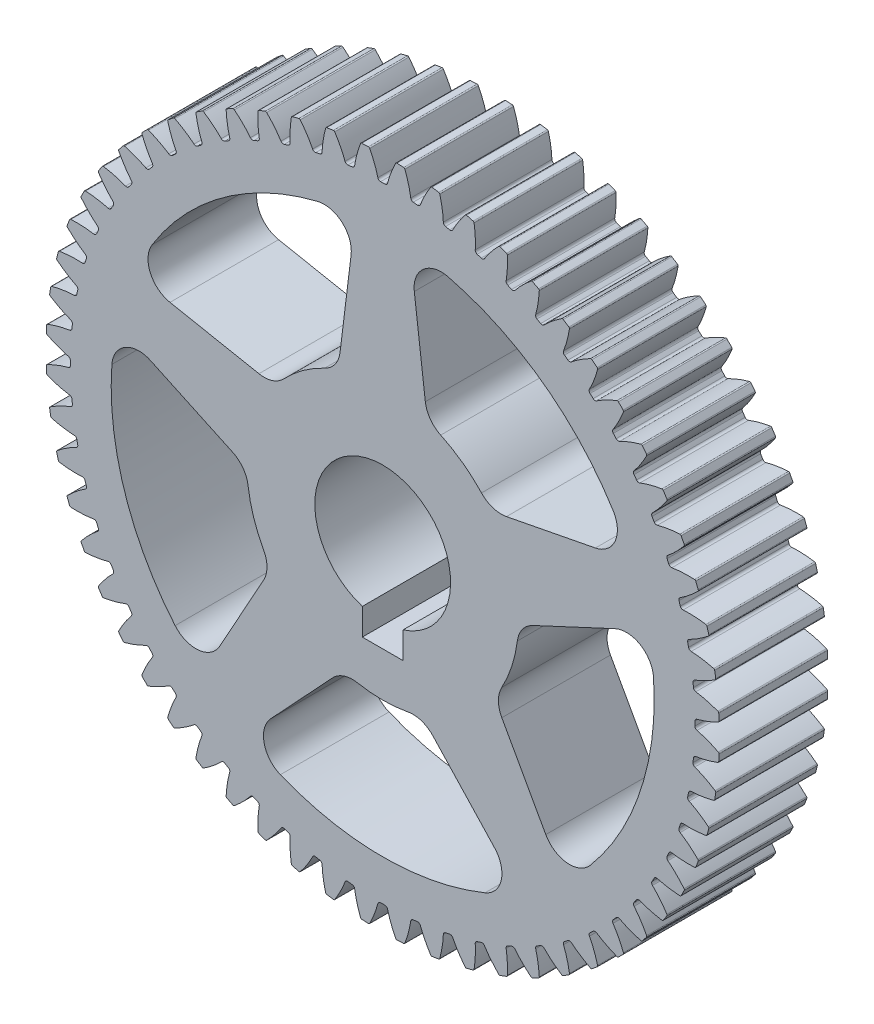
SolidWorks part; units mm, degrees
material "Alloy Steel"
ref_plane "Front" through (0, 0, 0) normal (0, 0, 1) x (1, 0, 0)
ref_plane "Top" through (0, 0, 0) normal (0, 1, 0) x (1, 0, 0)
ref_plane "Right" through (0, 0, 0) normal (1, 0, 0) x (0, 0, -1)
sketch "Sketch1" plane through (0, 0, 0) normal (0, 0, 1) x (1, 0, 0)
  circle A0 centre (0, 0) radius 39.37
  dimension "OutsideDiameter" = 78.74
extrude "Boss-Extrude1" add sketch "Sketch1" along normal blind 12.7
sketch "Sketch3" plane through (0, 0, 0) normal (0, 0, 1) x (1, 0, 0)
  line L0 (0, 0) -> (43.7181, 0) construction
  line L2 (0, 0) -> (-0.4117, 36.5102) construction
  line L3 (0, 0) -> (0.4117, 36.5102) construction
  line L4 (0.4117, 36.5102) -> (0.4037, 35.8) construction
  line L5 (0, 0) -> (0, 61.276) construction
  line L6 (-0.4117, 36.5102) -> (-0.4037, 35.8) construction
  circle A0 centre (0, 0) radius 39.37 construction
  circle A1 centre (0, 0) radius 38.1 construction
  circle A2 centre (0, 0) radius 35.8023 construction
  arc A3 (0.4117, 36.5102) -> (-0.4117, 36.5102) centre (0, 0) ccw construction
  arc A5 (1.5621, 39.339) -> (-1.5621, 39.339) centre (0, 0) ccw
  spline S0 degree 4 poles (-0.4037, 35.8) (-0.4038, 35.8056) (-0.4043, 35.8211) (-0.4059, 35.8504) (-0.4094, 35.8983) (-0.4152, 35.9593) (-0.4244, 36.0381) (-0.4372, 36.1309) (-0.4533, 36.2329) (-0.4732, 36.3438) (-0.4951, 36.4544) (-0.5188, 36.5646) (-0.5442, 36.6744) (-0.5769, 36.8074) (-0.6189, 36.9667) (-0.6721, 37.1529) (-0.7372, 37.3638) (-0.8088, 37.5787) (-0.8835, 37.7899) (-0.9639, 38.0031) (-1.0452, 38.2093) (-1.1346, 38.4233) (-1.2197, 38.6207) (-1.3206, 38.8416) (-1.4037, 39.0199) (-1.5193, 39.2547) (-1.5893, 39.3933) (-1.6733, 39.5555) (-1.7117, 39.6274) (-1.7353, 39.6717) knots 0 0 0 0 0 0.005377 0.015084 0.028532 0.04661 0.064855 0.092111 0.119476 0.146842 0.174209 0.201575 0.228941 0.256307 0.307035 0.361767 0.4165 0.471232 0.525964 0.580697 0.635429 0.690161 0.744894 0.799626 0.854358 0.909091 0.954545 1 1 1 1 1 construction
  spline S1 degree 4 poles (-0.4037, 35.8) (-0.4038, 35.8056) (-0.4043, 35.8211) (-0.4059, 35.8504) (-0.4094, 35.8983) (-0.4152, 35.9593) (-0.4244, 36.0381) (-0.4372, 36.1309) (-0.4533, 36.2329) (-0.4732, 36.3438) (-0.4951, 36.4544) (-0.5188, 36.5646) (-0.5442, 36.6744) (-0.5769, 36.8074) (-0.6189, 36.9667) (-0.6721, 37.1529) (-0.7372, 37.3638) (-0.8088, 37.5787) (-0.8835, 37.7899) (-0.9639, 38.0031) (-1.0452, 38.2093) (-1.1346, 38.4233) (-1.2197, 38.6207) (-1.3206, 38.8416) (-1.4037, 39.0199) (-1.4942, 39.2038) (-1.539, 39.2933) (-1.5621, 39.339) knots 0 0 0 0 0 0.005377 0.015084 0.028532 0.04661 0.064855 0.092111 0.119476 0.146842 0.174209 0.201575 0.228941 0.256307 0.307035 0.361767 0.4165 0.471232 0.525964 0.580697 0.635429 0.690161 0.744894 0.799626 0.854358 0.909091 0.909091 0.909091 0.909091 0.909091
  spline S2 degree 4 poles (0.4037, 35.8) (0.4038, 35.8056) (0.4043, 35.8211) (0.4059, 35.8504) (0.4094, 35.8983) (0.4152, 35.9593) (0.4244, 36.0381) (0.4372, 36.1309) (0.4533, 36.2329) (0.4732, 36.3438) (0.4951, 36.4544) (0.5188, 36.5646) (0.5442, 36.6744) (0.5769, 36.8074) (0.6189, 36.9667) (0.6721, 37.1529) (0.7372, 37.3638) (0.8088, 37.5787) (0.8835, 37.7899) (0.9639, 38.0031) (1.0452, 38.2093) (1.1346, 38.4233) (1.2197, 38.6207) (1.3206, 38.8416) (1.4037, 39.0199) (1.5193, 39.2547) (1.5893, 39.3933) (1.6733, 39.5555) (1.7117, 39.6274) (1.7353, 39.6717) knots 0 0 0 0 0 0.005377 0.015084 0.028532 0.04661 0.064855 0.092111 0.119476 0.146842 0.174209 0.201575 0.228941 0.256307 0.307035 0.361767 0.4165 0.471232 0.525964 0.580697 0.635429 0.690161 0.744894 0.799626 0.854358 0.909091 0.954545 1 1 1 1 1 construction
  spline S3 degree 4 poles (0.4037, 35.8) (0.4038, 35.8056) (0.4043, 35.8211) (0.4059, 35.8504) (0.4094, 35.8983) (0.4152, 35.9593) (0.4244, 36.0381) (0.4372, 36.1309) (0.4533, 36.2329) (0.4732, 36.3438) (0.4951, 36.4544) (0.5188, 36.5646) (0.5442, 36.6744) (0.5769, 36.8074) (0.6189, 36.9667) (0.6721, 37.1529) (0.7372, 37.3638) (0.8088, 37.5787) (0.8835, 37.7899) (0.9639, 38.0031) (1.0452, 38.2093) (1.1346, 38.4233) (1.2197, 38.6207) (1.3206, 38.8416) (1.4037, 39.0199) (1.4942, 39.2038) (1.539, 39.2933) (1.5621, 39.339) knots 0 0 0 0 0 0.005377 0.015084 0.028532 0.04661 0.064855 0.092111 0.119476 0.146842 0.174209 0.201575 0.228941 0.256307 0.307035 0.361767 0.4165 0.471232 0.525964 0.580697 0.635429 0.690161 0.744894 0.799626 0.854358 0.909091 0.909091 0.909091 0.909091 0.909091
  dimension "OutsideDiameter" = 78.74
  dimension "PitchCircle" = 76.2
  dimension "BaseCircle" = 71.6046
  dimension "DedendumCircle" = 73.025
sketch "DCLTBC" [suppressed] plane through (0, 0, 0) normal (0, 0, 1) x (1, 0, 0)
  line L0 (0, 0) -> (41.04, 0) construction
  line L1 (-0.5882, 26.2434) -> (-0.5952, 26.5563) construction
  line L2 (0.5882, 26.2434) -> (0.5952, 26.5563) construction
  line L3 (-0.5936, 26.4814) -> (-0.5952, 26.5563)
  line L4 (0.5936, 26.4814) -> (0.5952, 26.5563)
  line L5 (0, 0) -> (0, 104.9356) construction
  circle A0 centre (0, 0) radius 28.5
  circle A1 centre (0, 0) radius 27.5 construction
  circle A2 centre (0, 0) radius 26.563 construction
  arc A3 (0.5882, 26.2434) -> (-0.5882, 26.2434) centre (0, 0) ccw construction
  arc A4 (0.3512, 26.2477) -> (-0.3512, 26.2477) centre (0, 0) ccw
  arc A5 (-0.5936, 26.4814) -> (-0.3512, 26.2477) centre (-0.3544, 26.4868) ccw
  arc A7 (0.5936, 26.4814) -> (0.3512, 26.2477) centre (0.3544, 26.4868) cw
  spline S0 degree 4 poles (-999.0854, -27.9057) (-10.5882, 25.1883) (-0.7108, 25.7707) (-0.5671, 26.1913) (-0.5985, 26.609) (-0.6016, 26.6417) (-0.6063, 26.6839) (-0.6128, 26.7337) (-0.6209, 26.7885) (-0.6307, 26.8481) (-0.6414, 26.9075) (-0.653, 26.9669) (-0.6654, 27.026) (-0.6812, 27.0976) (-0.7015, 27.1836) (-0.7271, 27.2842) (-0.7584, 27.3983) (-0.7927, 27.5147) (-0.8284, 27.6294) (-0.8667, 27.7454) (-0.9054, 27.8577) (-0.948, 27.9745) (-0.9884, 28.0824) (-1.0364, 28.2034) (-1.2469, 28.7251) (-2.0615, 30.5023) (8.679, 5.7048) (-401.0337, 945.0216) knots -0.712101 -0.712101 -0.712101 -0.712101 -0.712101 0.005377 0.015084 0.028532 0.04661 0.064855 0.092111 0.119476 0.146842 0.174209 0.201575 0.228941 0.256307 0.307035 0.361767 0.4165 0.471232 0.525964 0.580697 0.635429 0.690161 0.744894 0.799626 0.854358 1.858481 1.858481 1.858481 1.858481 1.858481 only from (-0.5952, 26.5563) to (-1.151, 28.4767) construction
  spline S1 degree 4 poles (999.0854, -27.9056) (10.5882, 25.1883) (0.7108, 25.7707) (0.5671, 26.1913) (0.5985, 26.609) (0.6016, 26.6417) (0.6063, 26.6839) (0.6128, 26.7337) (0.6209, 26.7885) (0.6307, 26.8481) (0.6414, 26.9075) (0.653, 26.9669) (0.6654, 27.026) (0.6812, 27.0976) (0.7015, 27.1836) (0.7271, 27.2842) (0.7584, 27.3983) (0.7927, 27.5147) (0.8284, 27.6294) (0.8667, 27.7454) (0.9054, 27.8577) (0.948, 27.9745) (0.9884, 28.0824) (1.0364, 28.2034) (1.2469, 28.7251) (2.0615, 30.5023) (-8.679, 5.7048) (401.0337, 945.0216) knots -0.712101 -0.712101 -0.712101 -0.712101 -0.712101 0.005377 0.015084 0.028532 0.04661 0.064855 0.092111 0.119476 0.146842 0.174209 0.201575 0.228941 0.256307 0.307035 0.361767 0.4165 0.471232 0.525964 0.580697 0.635429 0.690161 0.744894 0.799626 0.854358 1.858481 1.858481 1.858481 1.858481 1.858481 only from (0.5952, 26.5563) to (1.151, 28.4767) construction
  spline S2 degree 4 poles (-0.5952, 26.5563) (-0.5953, 26.5593) (-0.5957, 26.5676) (-0.5966, 26.5833) (-0.5985, 26.609) (-0.6016, 26.6417) (-0.6063, 26.6839) (-0.6128, 26.7337) (-0.6209, 26.7885) (-0.6307, 26.8481) (-0.6414, 26.9075) (-0.653, 26.9669) (-0.6654, 27.026) (-0.6812, 27.0976) (-0.7015, 27.1836) (-0.7271, 27.2842) (-0.7584, 27.3983) (-0.7927, 27.5147) (-0.8284, 27.6294) (-0.8667, 27.7454) (-0.9054, 27.8577) (-0.948, 27.9745) (-0.9884, 28.0824) (-1.0364, 28.2034) (-1.0758, 28.3012) (-1.1188, 28.4023) (-1.14, 28.4516) (-1.151, 28.4767) knots 0 0 0 0 0 0.005377 0.015084 0.028532 0.04661 0.064855 0.092111 0.119476 0.146842 0.174209 0.201575 0.228941 0.256307 0.307035 0.361767 0.4165 0.471232 0.525964 0.580697 0.635429 0.690161 0.744894 0.799626 0.854358 0.909091 0.909091 0.909091 0.909091 0.909091
  spline S3 degree 4 poles (0.5952, 26.5563) (0.5953, 26.5593) (0.5957, 26.5676) (0.5966, 26.5833) (0.5985, 26.609) (0.6016, 26.6417) (0.6063, 26.6839) (0.6128, 26.7337) (0.6209, 26.7885) (0.6307, 26.8481) (0.6414, 26.9075) (0.653, 26.9669) (0.6654, 27.026) (0.6812, 27.0976) (0.7015, 27.1836) (0.7271, 27.2842) (0.7584, 27.3983) (0.7927, 27.5147) (0.8284, 27.6294) (0.8667, 27.7454) (0.9054, 27.8577) (0.948, 27.9745) (0.9884, 28.0824) (1.0364, 28.2034) (1.0758, 28.3012) (1.1188, 28.4023) (1.14, 28.4516) (1.151, 28.4767) knots 0 0 0 0 0 0.005377 0.015084 0.028532 0.04661 0.064855 0.092111 0.119476 0.146842 0.174209 0.201575 0.228941 0.256307 0.307035 0.361767 0.4165 0.471232 0.525964 0.580697 0.635429 0.690161 0.744894 0.799626 0.854358 0.909091 0.909091 0.909091 0.909091 0.909091
  dimension "OutsideDiameter" = 78.74
  dimension "PitchCircle" = 76.2
  dimension "BaseCircle" = 71.6046
  dimension "D1" = 0.3238
extrude "Cut-Extrude-DCLTBC" [suppressed] cut sketch "DCLTBC" along normal through all contours L4 S3 A0 S2 L3 A5 A4 A7
fillet "Fillet-DCLTBC" [suppressed] radius 0.1619
pattern_circular "CirPattern-DCLTBC" [suppressed] count 60 over 360 of bodies 111
sketch "DCGTBC" plane through (0, 0, 0) normal (0, 0, 1) x (1, 0, 0)
  line L0 (0, 0) -> (41.04, 0) construction
  line L5 (0, 0) -> (0, 104.9356) construction
  circle A0 centre (0, 0) radius 39.37
  circle A1 centre (0, 0) radius 38.1 construction
  circle A2 centre (0, 0) radius 35.8023 construction
  arc A3 (0.4117, 36.5102) -> (-0.4117, 36.5102) centre (0, 0) ccw construction
  arc A5 (0.2483, 36.5117) -> (0.5647, 36.7571) centre (0.2505, 36.8355) ccw
  arc A7 (-0.5647, 36.7571) -> (-0.2483, 36.5117) centre (-0.2505, 36.8355) ccw
  arc A11 (0.2483, 36.5117) -> (-0.2483, 36.5117) centre (0, 0) ccw
  spline S2 degree 4 poles (-999.6499, -2.7924) (-12.7117, 33.8816) (-0.5767, 34.6054) (-0.3619, 35.2517) (-0.4094, 35.8983) (-0.4152, 35.9593) (-0.4244, 36.0381) (-0.4372, 36.1309) (-0.4533, 36.2329) (-0.4732, 36.3438) (-0.4951, 36.4544) (-0.5188, 36.5646) (-0.5442, 36.6744) (-0.5769, 36.8074) (-0.6189, 36.9667) (-0.6721, 37.1529) (-0.7372, 37.3638) (-0.8088, 37.5787) (-0.8835, 37.7899) (-0.9639, 38.0031) (-1.0452, 38.2093) (-1.1346, 38.4233) (-1.2197, 38.6207) (-1.3206, 38.8416) (-1.7103, 39.6776) (-3.067, 42.2305) (11.3258, 13.5605) (-453.5509, 931.3527) knots -0.582806 -0.582806 -0.582806 -0.582806 -0.582806 0.005377 0.015084 0.028532 0.04661 0.064855 0.092111 0.119476 0.146842 0.174209 0.201575 0.228941 0.256307 0.307035 0.361767 0.4165 0.471232 0.525964 0.580697 0.635429 0.690161 0.744894 0.799626 0.854358 1.717039 1.717039 1.717039 1.717039 1.717039 only from (-0.4037, 35.8) to (-1.5621, 39.339) construction
  spline S3 degree 4 poles (999.6499, -2.7924) (12.7117, 33.8816) (0.5767, 34.6054) (0.3619, 35.2517) (0.4094, 35.8983) (0.4152, 35.9593) (0.4244, 36.0381) (0.4372, 36.1309) (0.4533, 36.2329) (0.4732, 36.3438) (0.4951, 36.4544) (0.5188, 36.5646) (0.5442, 36.6744) (0.5769, 36.8074) (0.6189, 36.9667) (0.6721, 37.1529) (0.7372, 37.3638) (0.8088, 37.5787) (0.8835, 37.7899) (0.9639, 38.0031) (1.0452, 38.2093) (1.1346, 38.4233) (1.2197, 38.6207) (1.3206, 38.8416) (1.7103, 39.6776) (3.067, 42.2305) (-11.3258, 13.5605) (453.5509, 931.3527) knots -0.582806 -0.582806 -0.582806 -0.582806 -0.582806 0.005377 0.015084 0.028532 0.04661 0.064855 0.092111 0.119476 0.146842 0.174209 0.201575 0.228941 0.256307 0.307035 0.361767 0.4165 0.471232 0.525964 0.580697 0.635429 0.690161 0.744894 0.799626 0.854358 1.717039 1.717039 1.717039 1.717039 1.717039 only from (0.4037, 35.8) to (1.5621, 39.339) construction
  spline S4 degree 4 poles (-0.5647, 36.7571) (-0.5698, 36.7775) (-0.5877, 36.8485) (-0.6209, 36.9737) (-0.6721, 37.1529) (-0.7372, 37.3638) (-0.8088, 37.5787) (-0.8835, 37.7899) (-0.9639, 38.0031) (-1.0452, 38.2093) (-1.1346, 38.4233) (-1.2197, 38.6207) (-1.3206, 38.8416) (-1.4037, 39.0199) (-1.4942, 39.2038) (-1.539, 39.2933) (-1.5621, 39.339) knots 0.235927 0.235927 0.235927 0.235927 0.235927 0.256307 0.307035 0.361767 0.4165 0.471232 0.525964 0.580697 0.635429 0.690161 0.744894 0.799626 0.854358 0.909091 0.909091 0.909091 0.909091 0.909091
  spline S5 degree 4 poles (0.5647, 36.7571) (0.5698, 36.7775) (0.5877, 36.8485) (0.6209, 36.9737) (0.6721, 37.1529) (0.7372, 37.3638) (0.8088, 37.5787) (0.8835, 37.7899) (0.9639, 38.0031) (1.0452, 38.2093) (1.1346, 38.4233) (1.2197, 38.6207) (1.3206, 38.8416) (1.4037, 39.0199) (1.4942, 39.2038) (1.539, 39.2933) (1.5621, 39.339) knots 0.235927 0.235927 0.235927 0.235927 0.235927 0.256307 0.307035 0.361767 0.4165 0.471232 0.525964 0.580697 0.635429 0.690161 0.744894 0.799626 0.854358 0.909091 0.909091 0.909091 0.909091 0.909091
  dimension "OutsideDiameter" = 78.74
  dimension "PitchCircle" = 76.2
  dimension "BaseCircle" = 71.6046
  dimension "D1" = 0.3238
extrude "Cut-Extrude-DCGTBC" cut sketch "DCGTBC" along normal through all contours A5 S5 A0 S4 A7 A11 region at (0, 38.2048, 0)
fillet "Fillet-DCGTBC" radius 0.1619 2 edges at (1.5621, 39.339, 6.35) (-1.5621, 39.339, 6.35)
pattern_circular "CirPattern-DCGTBC" count 60 over 360 about axis through (0, 0, 12.7) along (0, 0, 1) of "Cut-Extrude-DCGTBC", "Fillet-DCGTBC"
sketch "Sketch4" plane through (0, 0, 12.7) normal (0, 0, 1) x (1, 0, 0)
  circle A0 centre (0, 0) radius 4.7625
  dimension "D1" = 9.525
extrude "Cut-Extrude2" cut sketch "Sketch4" against normal through all
sketch "Sketch5" plane through (0, 0, 12.7) normal (0, 0, 1) x (1, 0, 0)
  circle A0 centre (0, 0) radius 7.9375
  dimension "D1" = 15.875
extrude "Cut-Extrude3" cut sketch "Sketch5" against normal through all
sketch "Sketch6" plane through (0, 0, 12.7) normal (0, 0, 1) x (1, 0, 0)
  line L0 (0, 0) -> (0, -7.9375) construction
  line L1 (2.3812, -5.1918) -> (-2.3813, -5.1918)
  line L2 (2.3812, -5.1918) -> (2.3813, -10.6832)
  line L3 (2.3813, -10.6832) -> (-2.3812, -10.6832)
  line L4 (-2.3813, -5.1918) -> (-2.3812, -10.6832)
  line L5 (2.3812, -5.1918) -> (-2.3812, -10.6832) construction
  line L6 (2.3813, -10.6832) -> (-2.3813, -5.1918) construction
  circle A0 centre (0, 0) radius 7.9375 construction
  point P0 (0, -7.9375)
  dimension "D1" = 4.7625
  dimension "D2" = 5.4915
extrude "Cut-Extrude4" cut sketch "Sketch6" against normal through all
sketch "Sketch7" plane through (0, 0, 12.7) normal (0, 0, 1) x (1, 0, 0)
  line L0 (0, 0) -> (0, 31.75) construction
  line L1 (-3.175, 31.5909) -> (-5.2127, 14.9948)
  line L2 (3.175, 31.5909) -> (5.2127, 14.9948)
  line L3 (29.0636, 12.7817) -> (12.65, 9.5913)
  line L4 (31.0258, 6.7425) -> (15.8717, -0.324)
  line L5 (21.1373, -23.6913) -> (13.0309, -9.067)
  line L6 (16, -27.4238) -> (4.5965, -15.195)
  line L7 (-16, -27.4238) -> (-4.5965, -15.195)
  line L8 (-21.1373, -23.6913) -> (-13.0309, -9.067)
  line L9 (-31.0258, 6.7425) -> (-15.8717, -0.324)
  line L10 (-29.0636, 12.7817) -> (-12.65, 9.5913)
  circle A0 centre (0, 0) radius 15.875
  circle A1 centre (0, 0) radius 31.75
  point P28 (0, 0)
  dimension "D1" = 31.75
  dimension "D2" = 63.5
  dimension "D3" = 7
  dimension "D4" = 6.35
  dimension "D5" = 5
extrude "Cut-Extrude5" cut sketch "Sketch7" against normal through all contours L1 A1 L10 A0 | L3 A1 L2 A0 | L5 A1 L4 A0 | L7 A1 L6 A0 | L9 A1 L8 A0 region at (-14.3235, 19.7146, 12.7) region at (14.3235, 19.7146, 12.7) region at (-23.1759, -7.5303, 12.7) region at (23.1759, -7.5303, 12.7) region at (0, -24.3686, 12.7)
fillet "Fillet1" radius 3.175 20 edges at (-4.5965, -15.195, 6.35) (4.5965, -15.195, 6.35) (16, -27.4238, 6.35) (-16, -27.4238, 6.35) (31.0258, 6.7425, 6.35) (21.1373, -23.6913, 6.35) (13.0309, -9.067, 6.35) (15.8717, -0.324, 6.35) (12.65, 9.5913, 6.35) (5.2127, 14.9948, 6.35) (3.175, 31.5909, 6.35) (29.0636, 12.7817, 6.35) (-15.8717, -0.324, 6.35) (-13.0309, -9.067, 6.35) (-31.0258, 6.7425, 6.35) (-21.1373, -23.6913, 6.35) (-3.175, 31.5909, 6.35) (-5.2127, 14.9948, 6.35) (-12.65, 9.5913, 6.35) (-29.0636, 12.7817, 6.35)
equation "\"DiametralPitch\"= 20'Diametral Pitch"
equation "\"NumTeeth\"= 60'Number of Teeth"
equation "\"PressureAngle\"= 20deg'Pressure Angle"
equation "\"Addendum\"= 1 / \"DiametralPitch\"'Addendum"
equation "\"Dedendum\"= 1.25 / \"DiametralPitch\"'Dedendum"
equation "\"WorkingDepth\"= 2 / \"DiametralPitch\"'Working Depth - here for REF (Not used in building model)"
equation "\"WholeDepth\"= 2.25 / \"DiametralPitch\"'Whole Depth - here for REF (Not used in building model)"
equation "\"Clearance\"= .19 / \"DiametralPitch\"'Clearance"
equation "\"CircularPitch\"= pi / \"DiametralPitch\"'Circular Pitch - here for REF (Not used in building model)"
equation "\"PitchCircle\"= \"NumTeeth\" / \"DiametralPitch\"'Pitch Circle - or - Pitch Diameter"
equation "\"OutsideDiameter\"= ( \"NumTeeth\" + 2 ) / \"DiametralPitch\"'Outside Diameter"
equation "\"Fillet\"= \"Clearance\" * cos ( \"PressureAngle\" ) * tan ( ( 90 + \"PressureAngle\" ) / 2 )'Fillet"
equation "\"AddendumCircle\"= \"PitchCircle\" + ( 2 * \"Addendum\" )'Addendum Circle - or - Addendum Diameter"
equation "\"DedendumCircle\"= \"PitchCircle\" - ( 2 * \"Dedendum\" )'Dedendum Circle - or - Dedendum Diameter"
equation "\"BaseCircle\"= \"PitchCircle\" * cos ( \"PressureAngle\" )'Base Circle - Base Diameter"
equation "\"PitchAngle\"= 360deg / \"NumTeeth\"'Pitch Angle"
equation "\"Alpha\"= sqr ( \"PitchCircle\" ^ 2 - \"BaseCircle\" ^ 2 ) / \"BaseCircle\" * 180 / PI - \"PressureAngle\"'Alpha - Used for Calculating Beta"
equation "\"Beta\"= ( \"PitchAngle\" / 4 - ( \"Alpha\" - 90 ) )'Beta - Used in definition of the parameters for the parametric equation driven curve"
equation "\"Gamma\"= ( \"PitchAngle\" / 4 - ( \"Alpha\" + 90 ) )'Gamma - Used in definition of the parameters for the parametric equation driven curve"
equation "\"Phi\"= sqr ( ( \"AddendumCircle\" / 2 ) ^ 2 - ( \"BaseCircle\" / 2 ) ^ 2 ) / ( \"BaseCircle\" / 2 )'Phi - Used in definition of the parameters for the parametric equation driven curve"
equation "\"DCGTBC\"= iif ( ( \"DedendumCircle\" + ( \"Fillet\" * 2 ) ) > \"BaseCircle\" , \"unsuppressed\" , \"suppressed\" )'if Dedendum Circle +2X Fillet IS GREATER THAN BaseCircle THEN Unsuppress OR Suppress FEATURE"
equation "\"DCLTBC\"= iif ( ( \"DedendumCircle\" + ( \"Fillet\" * 2 ) ) > \"BaseCircle\" , \"suppressed\" , \"unsuppressed\" )'if Dedendum Circle +2X Fillet IS GREATER THAN BaseCircle THEN Suppress OR Unsuppress FEATURE"
equation "\"Cut-Extrude-DCGTBC\"= iif ( ( \"DedendumCircle\" + ( \"Fillet\" * 2 ) ) > \"BaseCircle\" , \"unsuppressed\" , \"suppressed\" )'if Dedendum Circle +2X Fillet IS GREATER THAN BaseCircle THEN UnsuppressORSuppress FEATURE"
equation "\"Cut-Extrude-DCLTBC\"= iif ( ( \"DedendumCircle\" + ( \"Fillet\" * 2 ) ) > \"BaseCircle\" , \"suppressed\" , \"unsuppressed\" )'if Dedendum Circle +2X Fillet IS GREATER THAN BaseCircle THEN SuppressORUnsuppress FEATURE"
equation "\"CirPattern-DCGTBC\"= iif ( ( \"DedendumCircle\" + ( \"Fillet\" * 2 ) ) > \"BaseCircle\" , \"unsuppressed\" , \"suppressed\" )'if Dedendum Circle +2X Fillet IS GREATER THAN \"BaseCircle\" THEN UnsuppressORSuppress FEATURE"
equation "\"CirPattern-DCLTBC\"= iif ( ( \"DedendumCircle\" + ( \"Fillet\" * 2 ) ) > \"BaseCircle\" , \"suppressed\" , \"unsuppressed\" )'if Dedendum Circle +2X Fillet IS GREATER THAN \"BaseCircle\" THEN SuppressORUnsuppress FEATURE"
equation "\"Fillet-DCGTBC\"= iif ( ( \"DedendumCircle\" + ( \"Fillet\" * 2 ) ) > \"BaseCircle\" , \"unsuppressed\" , \"suppressed\" )'if Dedendum Circle +2X Fillet IS GREATER THAN \"BaseCircle\" THEN UnsuppressORSuppress FEATURE"
equation "\"Fillet-DCLTBC\"= iif ( ( \"DedendumCircle\" + ( \"Fillet\" * 2 ) ) > \"BaseCircle\" , \"suppressed\" , \"unsuppressed\" )'if Dedendum Circle +2X Fillet IS GREATER THAN \"BaseCircle\" THEN SuppressORUnsuppress FEATURE"
equation "\"D1@CirPattern-DCGTBC\"=\"NumTeeth\""
equation "\"D1@CirPattern-DCLTBC\"=\"NumTeeth\""
equation "\"D1@DCGTBC\"=\"Fillet\""
equation "\"D1@DCLTBC\"=\"Fillet\""
equation "\"D1@Fillet-DCLTBC\"=\"Fillet\"/2"
equation "\"D1@Fillet-DCGTBC\"=\"Fillet\"/2"
